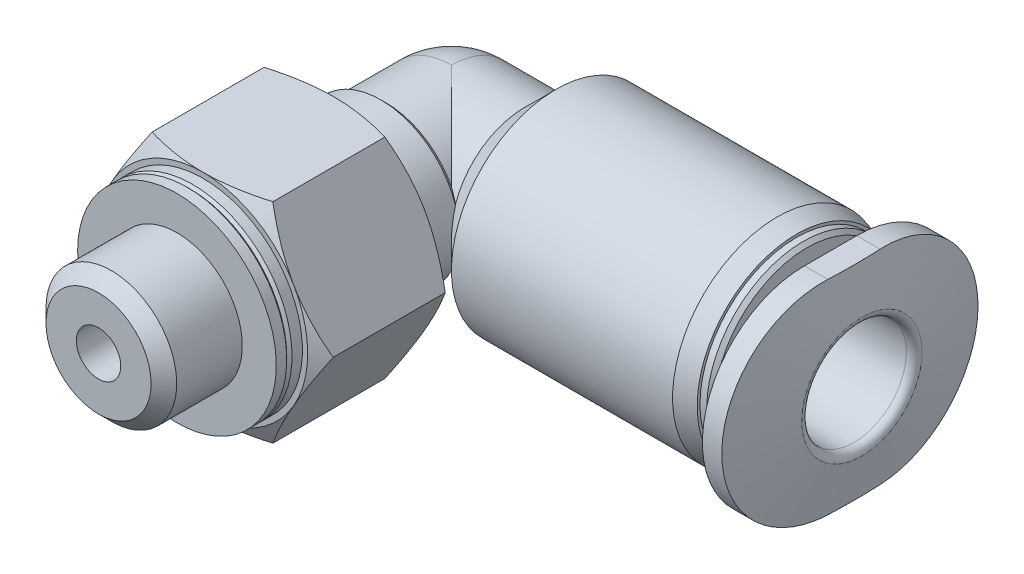
SolidWorks part; units mm, degrees
ref_plane "Front Plane" through (0, 0, 0) normal (0, 0, 1) x (1, 0, 0)
ref_plane "Top Plane" through (0, 0, 0) normal (0, 1, 0) x (1, 0, 0)
ref_plane "Right Plane" through (0, 0, 0) normal (1, 0, 0) x (0, 0, -1)
sketch "Sketch1" plane through (0, 0, 0) normal (0, 0, 1) x (1, 0, 0)
  line L0 (0, 2.8) -> (2.8, 2.8)
  line L1 (2.8, 2.8) -> (4, 4)
  line L2 (4, 4) -> (12.4571, 4)
  line L3 (12.4571, 4) -> (13.2, 3.801)
  line L4 (13.2, 3.801) -> (13.2, 3.6938)
  line L5 (13.2, 3.6938) -> (13.4586, 3.6938)
  line L6 (13.4586, 3.6938) -> (13.6, 3.5524)
  line L7 (13.6, 3.5524) -> (13.6, 2.5)
  line L8 (13.6, 2.5) -> (14.13, 2.5)
  line L9 (14.5, 2.87) -> (14.5, 5.9)
  line L10 (14.5, 5.9) -> (14.8974, 5.9)
  line L11 (15.0944, 5.7347) -> (15.7, 2.3)
  line L12 (15.7, 2.3) -> (15.7, 0)
  line L13 (15.7, 0) -> (-2.8, 0)
  line L14 (15.7, 0) -> (-2.8, 0) construction
  arc A0 (-2.8, 0) -> (0, 2.8) centre (0, 0) cw
  arc A1 (14.13, 2.5) -> (14.5, 2.87) centre (14.13, 2.87) ccw
  arc A2 (14.8974, 5.9) -> (15.0944, 5.7347) centre (14.8974, 5.7) cw
revolve "Revolve1" add sketch "Sketch1" angle 360 about L14
sketch "Sketch2" plane through (0, 0, 0) normal (1, 0, 0) x (0, 0, -1)
  line L0 (-10.5, 0) -> (-10.5, 3.8)
  line L1 (-10.5, 3.8) -> (-10.1, 3.8)
  line L2 (-10.1, 3.8) -> (-10, 3.7)
  line L3 (-10, 3.7) -> (-9.9, 3.8)
  line L4 (-9.9, 3.8) -> (-9.5, 3.8)
  line L5 (-9.5, 3.8) -> (-9.5, 4)
  line L6 (-9.5, 4) -> (-9.1305, 4.64)
  line L7 (-9.1305, 4.64) -> (-4.8695, 4.64)
  line L8 (-4.8695, 4.64) -> (-4.5, 4)
  line L9 (-4.5, 4) -> (-4.5, 3)
  line L10 (-4.5, 3) -> (-2.7, 3)
  line L11 (-2.7, 3) -> (-2.5, 2.8)
  line L12 (-2.5, 2.8) -> (0, 2.8)
  line L13 (0, 2.8) -> (0, 0)
  line L14 (0, 0) -> (-10.5, 0)
  line L15 (0, 0) -> (-10.5, 0) construction
revolve "Revolve2" add sketch "Sketch2" angle 360 about L15
sketch "Sketch3" plane through (0, 0, 0) normal (1, 0, 0) x (0, 0, -1)
  line L0 (-13.5, 0) -> (-13.5, 2.0095)
  line L1 (-13.5, 2.0095) -> (-13.0095, 2.5)
  line L2 (-13.0095, 2.5) -> (-10.5, 2.5)
  line L3 (-10.5, 2.5) -> (-10.5, 0)
  line L4 (-10.5, 0) -> (-13.5, 0)
  line L5 (-10.5, 0) -> (-13.5, 0) construction
revolve "Revolve3" add sketch "Sketch3" angle 360 about L5
cosmetic thread "Cosmetic Thread1" parameters "D1"=3, "D2"=4.019
ref_plane "Plane1" through (15.7, 0, 0) normal (1, 0, 0) x (0, 0, -1)
sketch "Sketch4" plane through (15.7, 0, 0) normal (1, 0, 0) x (0, 0, -1)
  line L0 (-9.8, -5.658) -> (0, -11.3161)
  line L1 (0, -11.3161) -> (9.8, -5.658)
  line L2 (9.8, -5.658) -> (9.8, 5.658)
  line L3 (9.8, 5.658) -> (0, 11.3161)
  line L4 (0, 11.3161) -> (-9.8, 5.658)
  line L5 (-9.8, 5.658) -> (-9.8, -5.658)
  line L6 (-1, -3.9) -> (1, -3.9)
  line L7 (1, 3.9) -> (-1, 3.9)
  arc A0 (-1, 3.9) -> (-1, -3.9) centre (-1, 0) ccw
  arc A1 (1, -3.9) -> (1, 3.9) centre (1, 0) ccw
extrude "Cut-Extrude1" cut sketch "Sketch4" against normal blind 1.2
sketch "Sketch5" plane through (0, 0, 0) normal (0, 1, 0) x (1, 0, 0)
  line L0 (0, 0.85) -> (4.1, 0.85)
  line L1 (4.1, 0.85) -> (4.1, 2)
  line L2 (4.1, 2) -> (15.4, 2)
  line L3 (15.7, 2.3) -> (15.7, 0)
  line L4 (15.7, 0) -> (-0.85, 0)
  line L5 (15.7, 0) -> (-0.85, 0) construction
  arc A0 (-0.85, 0) -> (0, 0.85) centre (0, 0) cw
  arc A1 (15.4, 2) -> (15.7, 2.3) centre (15.4, 2.3) ccw
sketch "Sketch6" plane through (0, 0, 0) normal (1, 0, 0) x (0, 0, -1)
  line L0 (-13.5, 0) -> (-13.5, 0.85)
  line L1 (-13.5, 0.85) -> (0, 0.85)
  line L2 (0, 0.85) -> (0, 0)
  line L3 (0, 0) -> (-13.5, 0)
  line L4 (0, 0) -> (-13.5, 0) construction
revolve "Cut-Revolve1" cut sketch "Sketch6" angle 360 about L4
revolve "Cut-Revolve2" cut sketch "Sketch5" angle 360 about L5
ref_plane "Plane2" through (0, 0, 10.5) normal (0, 0, 1) x (1, 0, 0)
sketch "Sketch7" plane through (0, 0, 10.5) normal (0, 0, 1) x (1, 0, 0)
  line L0 (-8, -8) -> (8, -8)
  line L1 (8, -8) -> (8, 8)
  line L2 (8, 8) -> (-8, 8)
  line L3 (-8, 8) -> (-8, -8)
  line L4 (-4.6188, 0) -> (-2.3094, -4)
  line L5 (-2.3094, -4) -> (2.3094, -4)
  line L6 (2.3094, -4) -> (4.6188, 0)
  line L7 (4.6188, 0) -> (2.3094, 4)
  line L8 (2.3094, 4) -> (-2.3094, 4)
  line L9 (-2.3094, 4) -> (-4.6188, 0)
extrude "Cut-Extrude2" cut sketch "Sketch7" against normal blind 6.0556
ref_plane "Plane3" through (0, 0, 10.5) normal (0, 0, 1) x (1, 0, 0)
ref_plane "Plane4" through (4.1, 0, 0) normal (1, 0, 0) x (0, 0, -1)
ref_plane "ANBAU XY" through (0, 0, 10.5) normal (0, 0, 1) x (1, 0, 0)
ref_plane "ANBAU XZ" through (0, 0, 0) normal (0, -1, 0) x (-1, 0, 0)
ref_plane "ANBAU YZ" through (0, 0, 0) normal (1, 0, 0) x (0, 0, -1)
ref_axis "ANBAU X" through (-80.9, 0, 10.5) along (1, 0, 0)
ref_axis "ANBAU Y" through (0, -50, 10.5) along (0, 1, 0)
ref_axis "ANBAU Z" through (0, 0, 80.9) along (0, 0, -1)
sketch3d "ANBAU"
  point P0 (0, 0, 10.5)
ref_plane "ANBAU_STD XY" through (0, 0, 10.5) normal (0, 0, -1) x (-1, 0, 0)
ref_plane "ANBAU_STD XZ" through (0, 0, 0) normal (0, 1, 0) x (1, 0, 0)
ref_plane "ANBAU_STD YZ" through (0, 0, 0) normal (1, 0, 0) x (0, 0, -1)
ref_axis "ANBAU_STD X" through (-80.9, 0, 10.5) along (1, 0, 0)
ref_axis "ANBAU_STD Y" through (0, 50, 10.5) along (0, -1, 0)
ref_axis "ANBAU_STD Z" through (0, 0, -80.9) along (0, 0, 1)
sketch3d "ANBAU_STD"
  point P0 (0, 0, 10.5)
ref_plane "CPV XY" through (0, 0, 10.5) normal (0, 0, -1) x (-1, 0, 0)
ref_plane "CPV XZ" through (0, 0, 0) normal (0, 1, 0) x (1, 0, 0)
ref_plane "CPV YZ" through (0, 0, 0) normal (1, 0, 0) x (0, 0, -1)
ref_axis "CPV X" through (-80.9, 0, 10.5) along (1, 0, 0)
ref_axis "CPV Y" through (0, 50, 10.5) along (0, -1, 0)
ref_axis "CPV Z" through (0, 0, -80.9) along (0, 0, 1)
sketch3d "CPV"
  point P0 (0, 0, 10.5)
ref_plane "FDT_MOUNT XY" through (0, 0, 10.5) normal (0, 0, 1) x (1, 0, 0)
ref_plane "FDT_MOUNT XZ" through (0, 0, 0) normal (1, 0, 0) x (0, 0, -1)
ref_plane "FDT_MOUNT YZ" through (0, 0, 0) normal (0, 1, 0) x (1, 0, 0)
ref_axis "FDT_MOUNT X" through (0, -50, 10.5) along (0, 1, 0)
ref_axis "FDT_MOUNT Y" through (80.9, 0, 10.5) along (-1, 0, 0)
ref_axis "FDT_MOUNT Z" through (0, 0, 50) along (0, 0, -1)
sketch3d "FDT_MOUNT"
  point P0 (0, 0, 10.5)
ref_plane "FDT_SCHLAUCH XY" through (4.1, 0, 0) normal (1, 0, 0) x (0, 0, -1)
ref_plane "FDT_SCHLAUCH XZ" through (0, 0, 0) normal (0, -1, 0) x (-1, 0, 0)
ref_plane "FDT_SCHLAUCH YZ" through (0, 0, 0) normal (0, 0, -1) x (-1, 0, 0)
ref_axis "FDT_SCHLAUCH X" through (4.1, 0, 80.9) along (0, 0, -1)
ref_axis "FDT_SCHLAUCH Y" through (4.1, -50, 0) along (0, 1, 0)
ref_axis "FDT_SCHLAUCH Z" through (80.9, 0, 0) along (-1, 0, 0)
sketch3d "FDT_SCHLAUCH"
  point P0 (4.1, 0, 0)
